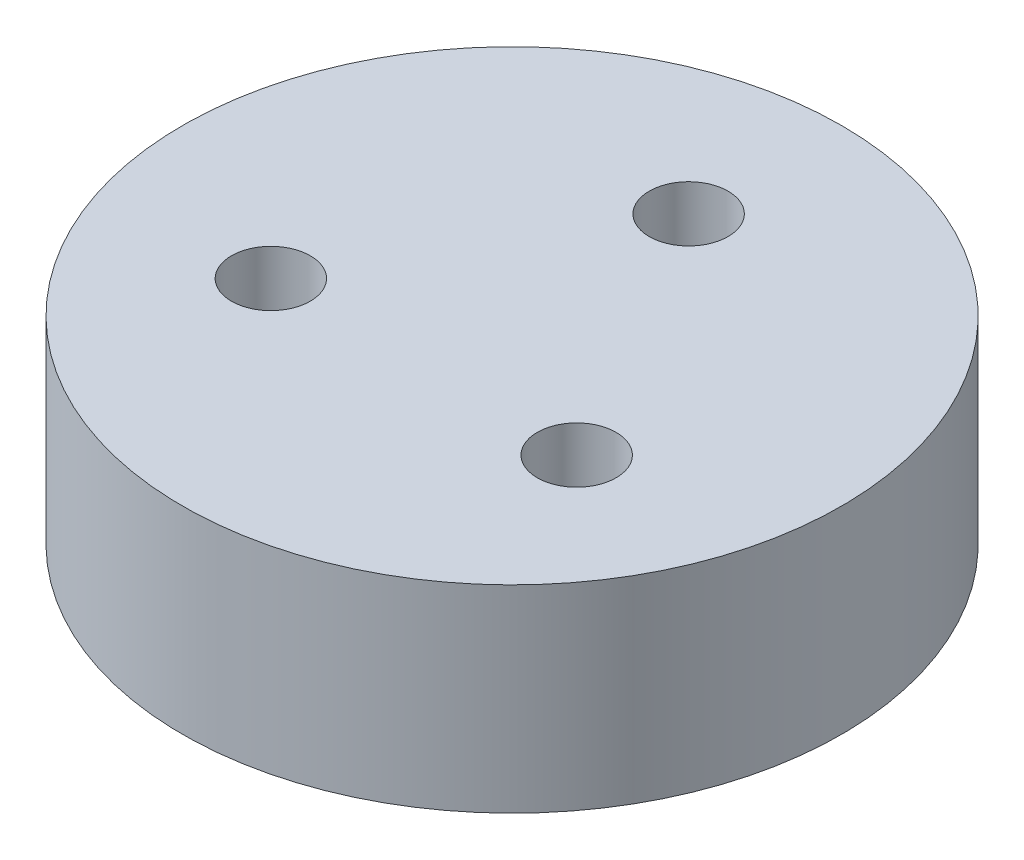
SolidWorks part; units mm, degrees
ref_plane "Front Plane" through (0, 0, 0) normal (0, 0, 1) x (1, 0, 0)
ref_plane "Top Plane" through (0, 0, 0) normal (0, 1, 0) x (1, 0, 0)
ref_plane "Right Plane" through (0, 0, 0) normal (1, 0, 0) x (0, 0, -1)
sketch "Sketch1" plane through (0, 0, 0) normal (0, 1, 0) x (1, 0, 0)
  circle A0 centre (0, 0) radius 6.35
  circle A1 centre (0, 0) radius 15.875
  dimension "D1" = 12.7
  dimension "D2" = 31.75
extrude "Boss-Extrude1" add sketch "Sketch1" along normal blind 9.525
sketch "Sketch2" plane through (0, 9.525, 0) normal (0, 1, 0) x (1, 0, 0)
  line L0 (0, 8.5055) -> (-7.366, -4.2528) construction
  line L1 (-7.366, -4.2528) -> (7.366, -4.2528) construction
  line L2 (7.366, -4.2528) -> (0, 8.5055) construction
  line L3 (0, 8.5055) -> (0, 0) construction
  line L4 (0, 0) -> (7.366, -4.2528) construction
  line L5 (0, 0) -> (-7.366, -4.2528) construction
  point P5 (0, -4.2528)
  dimension "D1" = 14.732
hole_wizard "#6 Clearance Hole1" positions "Sketch3" profile "Sketch4" hole size "#6" standard "ANSI Inch" end condition up to next
sketch "Sketch3" plane through (0, 9.525, 0) normal (0, 1, 0) x (1, 0, 0)
  point P0 (0, 8.5055)
  point P3 (-7.366, -4.2528)
  point P6 (7.366, -4.2528)
sketch "Sketch4" plane through (0, 9.525, -8.5055) normal (1, 0, 0) x (0, 0, 1)
  line L0 (0, 0) -> (0, 9.525)
  line L1 (0, 9.525) -> (1.8986, 9.525)
  line L2 (1.8986, 9.525) -> (1.8986, 0)
  line L5 (1.8986, 0) -> (0, 0)
  line L11 (0, -6.35) -> (0, 107.95) construction
  dimension "Thru Hole Dia." = 3.7973
  dimension "Thru Hole Depth" = 9.525
sketch "Sketch5" plane through (0, 9.525, 0) normal (0, 1, 0) x (1, 0, 0)
  circle A0 centre (0, 0) radius 6.35 construction
  circle A1 centre (0, 0) radius 6.35
extrude "Boss-Extrude2" add sketch "Sketch5" against normal blind 6.35
